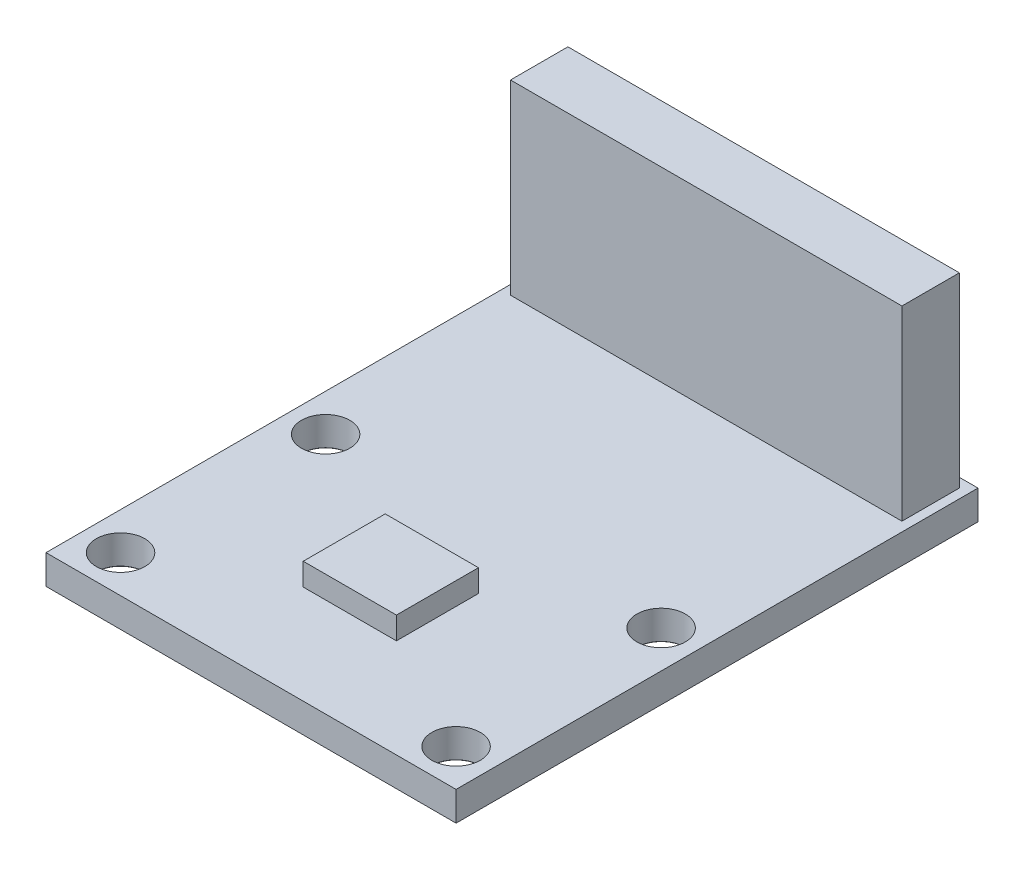
SolidWorks part; units mm, degrees
material "Massless"
ref_plane "Front Plane" through (0, 0, 0) normal (0, 0, 1) x (1, 0, 0)
ref_plane "Top Plane" through (0, 0, 0) normal (0, 1, 0) x (1, 0, 0)
ref_plane "Right Plane" through (0, 0, 0) normal (1, 0, 0) x (0, 0, -1)
ref_axis "X Axis" through (88.99, 0, 0) along (-1, 0, 0)
ref_axis "Y Axis" through (0, 55, 0) along (0, -1, 0)
ref_axis "Z Axis" through (0, 0, -88.99) along (0, 0, 1)
sketch "Sketch1" plane through (0, 0, 0) normal (0, 1, 0) x (1, 0, 0)
  line L1 (-11, 20.5) -> (11, 20.5)
  line L2 (-11, 20.5) -> (-11, -7.5)
  line L3 (-11, -7.5) -> (11, -7.5)
  line L4 (11, 20.5) -> (11, -7.5)
  line L5 (0, -7.5) -> (0, 20.5) construction
  line L6 (-11, 6.5) -> (11, 6.5) construction
  line L7 (9, -5.5) -> (-9, -5.5) construction
  line L8 (9, -5.5) -> (9, 5.5) construction
  line L9 (9, 5.5) -> (-9, 5.5) construction
  line L10 (-9, -5.5) -> (-9, 5.5) construction
  line L11 (0, 5.5) -> (0, -5.5) construction
  line L12 (9, 0) -> (-9, 0) construction
  line L13 (11, -7.5) -> (9, -7.5) construction
  line L14 (11, -7.5) -> (11, -5.5) construction
  line L15 (11, -5.5) -> (9, -5.5) construction
  line L16 (9, -7.5) -> (9, -5.5) construction
  point P0 (0, 6.5)
  point P4 (0, 0)
  dimension "D1" = 28
  dimension "D2" = 22
  dimension "D3" = 18
  dimension "D4" = 11
extrude "Boss-Extrude1" add sketch "Sketch1" along normal blind 1.57
sketch "Sketch4" plane through (0, 1.57, 0) normal (0, 1, 0) x (1, 0, 0)
  point P0 (-9, 5.5)
  point P3 (-9, -5.5)
  point P6 (9, -5.5)
  point P9 (9, 5.5)
hole_wizard "Ø2.6 (2.6) Diameter Hole1" positions "Sketch4" profile "Sketch3" hole size "Ø2.6" standard "ANSI Metric" end condition up to next
sketch "Sketch3" plane through (-9, 1.57, -5.5) normal (1, 0, 0) x (0, 0, 1)
  line L0 (0, 0) -> (0, 1.57)
  line L1 (0, 1.57) -> (1.325, 1.57)
  line L2 (1.3, 1.545) -> (1.3, 0)
  line L5 (1.3, 0) -> (0, 0)
  line L7 (1.325, 1.57) -> (1.3, 1.545)
  line L8 (-1.325, 1.57) -> (-1.3, 1.545) construction
  line L11 (0, -6.35) -> (0, 107.95) construction
  dimension "Thru Hole Dia." = 2.6
  dimension "Thru Hole Depth" = 1.57
  dimension "Far C'Sink Dia." = 2.65
  dimension "Far C'Sink Angle" = 90
sketch "Sketch5" plane through (0, 1.57, 0) normal (0, 1, 0) x (1, 0, 0)
  line L1 (-2.5, -2.2) -> (2.5, -2.2)
  line L2 (-2.5, -2.2) -> (-2.5, 2.2)
  line L3 (-2.5, 2.2) -> (2.5, 2.2)
  line L4 (2.5, -2.2) -> (2.5, 2.2)
  line L5 (0, 2.2) -> (0, -2.2) construction
  line L6 (-2.5, 0) -> (2.5, 0) construction
  point P0 (0, 0)
  dimension "D1" = 5
  dimension "D2" = 4.4
extrude "Boss-Extrude2" add sketch "Sketch5" along normal blind 1.2
sketch "Sketch6" plane through (0, 1.57, 0) normal (0, 1, 0) x (1, 0, 0)
  line L0 (11, 20.5) -> (11, -7.5) construction
  line L1 (-11, 20.5) -> (11, 20.5) construction
  line L2 (-11, 20.5) -> (-11, 16.42) construction
  line L3 (-11, 16.42) -> (11, 16.42) construction
  line L4 (11, 20.5) -> (11, 16.42) construction
  line L5 (-10.5, 20) -> (10.5, 20)
  line L6 (10.5, 20) -> (10.5, 16.92)
  line L7 (-10.5, 16.92) -> (10.5, 16.92)
  line L8 (-10.5, 20) -> (-10.5, 16.92)
  dimension "D1" = 4.08
  dimension "D2" = 0.5
extrude "Boss-Extrude3" add sketch "Sketch6" along normal blind 10
